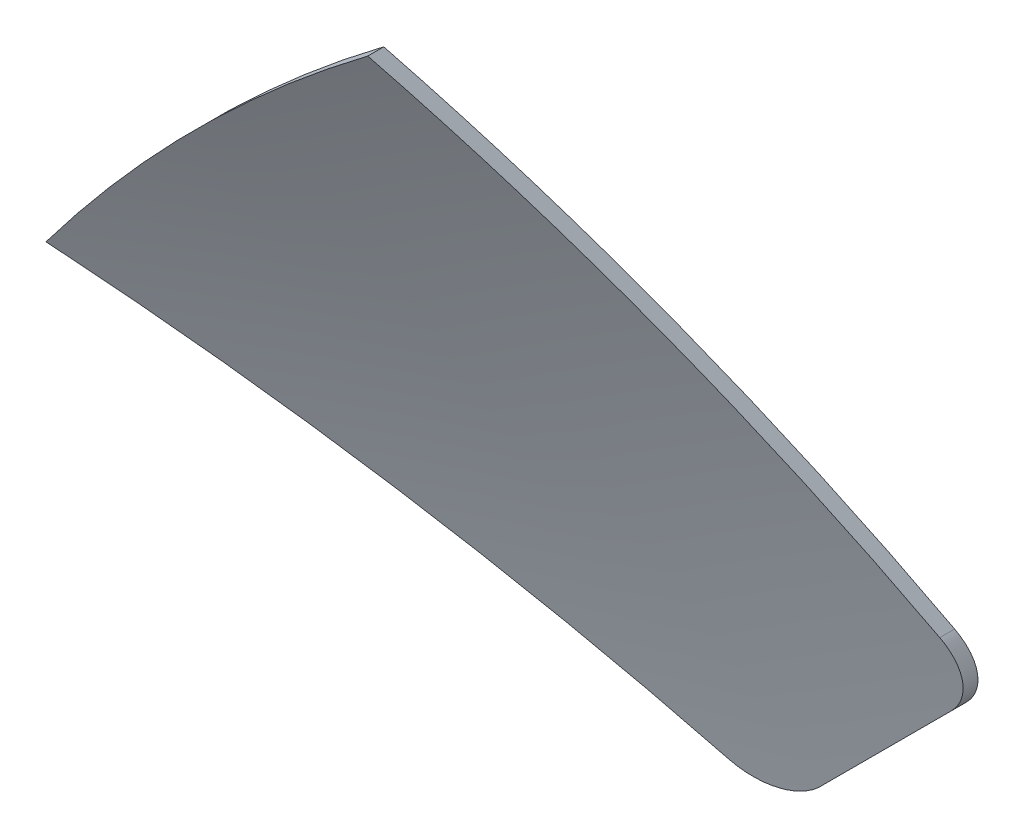
SolidWorks part; units mm, degrees
ref_plane "前视基准面" through (0, 0, 0) normal (0, 0, 1) x (1, 0, 0)
ref_plane "上视基准面" through (0, 0, 0) normal (0, 1, 0) x (1, 0, 0)
ref_plane "右视基准面" through (0, 0, 0) normal (1, 0, 0) x (0, 0, -1)
sketch "草图1" plane through (0, 0, 0) normal (0, 0, 1) x (1, 0, 0)
  line L1 (0, 0) -> (-53.033, 53.033) construction
  line L2 (-45.9215, 34.6044) -> (-28.6922, 21.6211)
  line L3 (-28.6922, 21.6211) -> (-21.6211, 28.6922)
  line L4 (-34.6044, 45.9215) -> (-21.6211, 28.6922)
  circle A0 centre (0, 0) radius 75 construction
  arc A3 (-34.6044, 45.9215) -> (-45.9215, 34.6044) centre (0, 0) ccw
  point P13 (-25.1566, 25.1566)
  point P29 (0, 0)
  dimension "D2" = 5
  dimension "D3" = 8
sketch "草图2" plane through (0, 0, 0) normal (0, 0, 1) x (1, 0, 0)
  line L0 (0, 151.6709) -> (0, -166.8188) construction
  line L1 (0, -125.2) -> (0, 125.2)
  arc A0 (0, 125.2) -> (0, -125.2) centre (0, 0) ccw
revolve "旋转1" add sketch "草图2" angle 180 about L0
shell "抽壳1" thickness 0.5
extrude "切除-拉伸1" cut sketch "草图1" against normal blind 323 flip side to cut contours L4 L3 L2 A3
fillet "圆角1" radius 2 2 edges at (-28.6922, 21.6211, -120.1956) (-21.6211, 28.6922, -120.1956)
